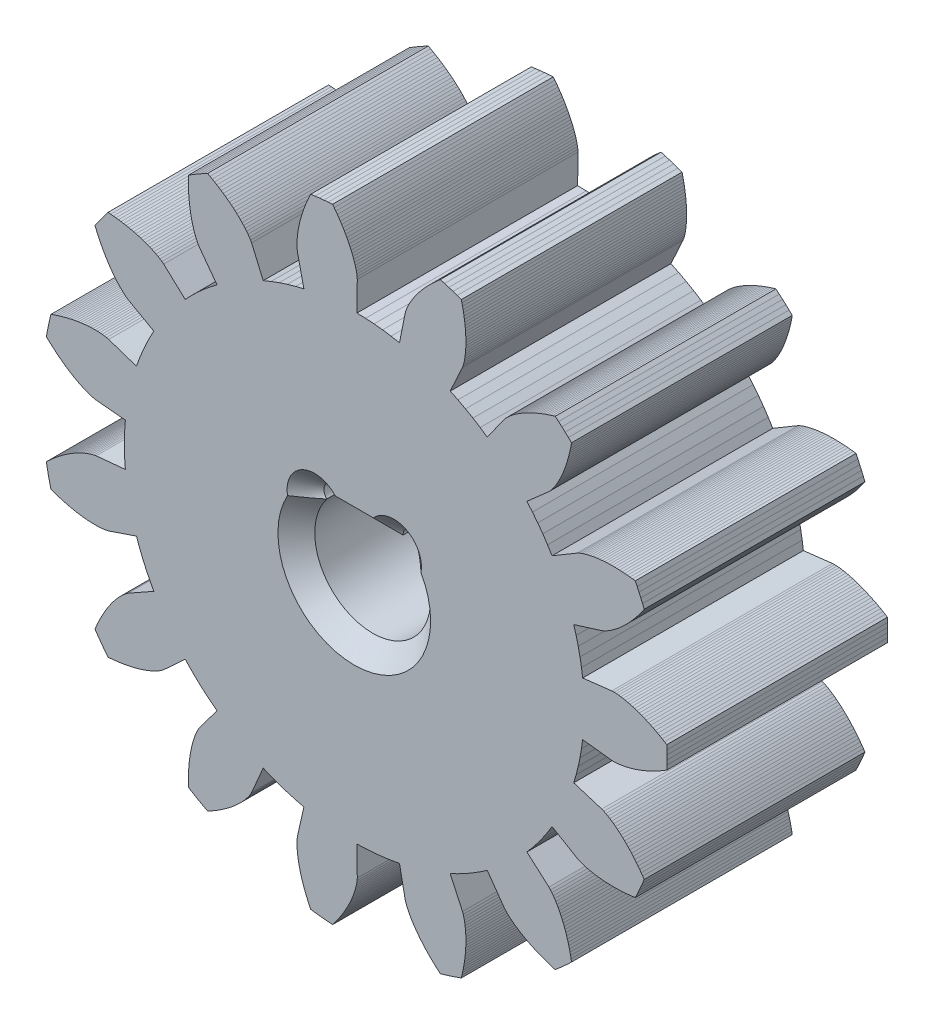
SolidWorks part; units mm, degrees
ref_plane "Front Plane" through (0, 0, 0) normal (0, 0, 1) x (1, 0, 0)
ref_plane "Top Plane" through (0, 0, 0) normal (0, 1, 0) x (1, 0, 0)
ref_plane "Right Plane" through (0, 0, 0) normal (1, 0, 0) x (0, 0, -1)
sketch "Model" plane through (0, 0, 0) normal (0, 0, 1) x (1, 0, 0)
  line L0 (6.2078, -0.7252) -> (7.0001, -0.8177)
  line L1 (7.0001, -0.8177) -> (7.0608, -0.8195)
  line L2 (7.0608, -0.8195) -> (7.122, -0.8168)
  line L3 (7.122, -0.8168) -> (7.1836, -0.8111)
  line L4 (7.1836, -0.8111) -> (7.2454, -0.803)
  line L5 (7.2454, -0.803) -> (7.3074, -0.7927)
  line L6 (7.3074, -0.7927) -> (7.3696, -0.7805)
  line L7 (7.3696, -0.7805) -> (7.4319, -0.7664)
  line L8 (7.4319, -0.7664) -> (7.4943, -0.7506)
  line L9 (7.4943, -0.7506) -> (7.5568, -0.7331)
  line L10 (7.5568, -0.7331) -> (7.6194, -0.714)
  line L11 (7.6194, -0.714) -> (7.6821, -0.6934)
  line L12 (7.6821, -0.6934) -> (7.7448, -0.6713)
  line L13 (7.7448, -0.6713) -> (7.8075, -0.6477)
  line L14 (7.8075, -0.6477) -> (7.8703, -0.6228)
  line L15 (7.8703, -0.6228) -> (7.933, -0.5964)
  line L16 (7.933, -0.5964) -> (7.9957, -0.5686)
  line L17 (7.9957, -0.5686) -> (8.0584, -0.5396)
  line L18 (8.0584, -0.5396) -> (8.121, -0.5091)
  line L19 (8.121, -0.5091) -> (8.1835, -0.4774)
  line L20 (8.1835, -0.4774) -> (8.246, -0.4444)
  line L21 (8.246, -0.4444) -> (8.3083, -0.4102)
  line L22 (8.3083, -0.4102) -> (8.3706, -0.3746)
  line L23 (8.3706, -0.3746) -> (8.4327, -0.3378)
  line L24 (8.4327, -0.3378) -> (8.4947, -0.2998)
  line L25 (8.4947, -0.2998) -> (8.4981, -0.1799)
  line L26 (8.4981, -0.1799) -> (8.4998, -0.06)
  line L27 (8.4998, -0.06) -> (8.4998, 0.06)
  line L28 (8.4998, 0.06) -> (8.4981, 0.1799)
  line L29 (8.4981, 0.1799) -> (8.4947, 0.2998)
  line L30 (8.4947, 0.2998) -> (8.4327, 0.3378)
  line L31 (8.4327, 0.3378) -> (8.3706, 0.3746)
  line L32 (8.3706, 0.3746) -> (8.3083, 0.4102)
  line L33 (8.3083, 0.4102) -> (8.246, 0.4444)
  line L34 (8.246, 0.4444) -> (8.1835, 0.4774)
  line L35 (8.1835, 0.4774) -> (8.121, 0.5091)
  line L36 (8.121, 0.5091) -> (8.0584, 0.5396)
  line L37 (8.0584, 0.5396) -> (7.9957, 0.5686)
  line L38 (7.9957, 0.5686) -> (7.933, 0.5964)
  line L39 (7.933, 0.5964) -> (7.8703, 0.6228)
  line L40 (7.8703, 0.6228) -> (7.8075, 0.6477)
  line L41 (7.8075, 0.6477) -> (7.7448, 0.6713)
  line L42 (7.7448, 0.6713) -> (7.6821, 0.6934)
  line L43 (7.6821, 0.6934) -> (7.6194, 0.714)
  line L44 (7.6194, 0.714) -> (7.5568, 0.7331)
  line L45 (7.5568, 0.7331) -> (7.4943, 0.7506)
  line L46 (7.4943, 0.7506) -> (7.4319, 0.7664)
  line L47 (7.4319, 0.7664) -> (7.3696, 0.7805)
  line L48 (7.3696, 0.7805) -> (7.3074, 0.7927)
  line L49 (7.3074, 0.7927) -> (7.2454, 0.803)
  line L50 (7.2454, 0.803) -> (7.1836, 0.8111)
  line L51 (7.1836, 0.8111) -> (7.122, 0.8168)
  line L52 (7.122, 0.8168) -> (7.0608, 0.8195)
  line L53 (7.0608, 0.8195) -> (7.0001, 0.8177)
  line L54 (7.0001, 0.8177) -> (6.2078, 0.7252)
  line L55 (6.2078, 0.7252) -> (6.1765, 0.9559)
  line L56 (6.1765, 0.9559) -> (6.1366, 1.1853)
  line L57 (6.1366, 1.1853) -> (6.0881, 1.4131)
  line L58 (6.0881, 1.4131) -> (6.0313, 1.6389)
  line L59 (6.0313, 1.6389) -> (5.9661, 1.8624)
  line L60 (5.9661, 1.8624) -> (6.7275, 2.1002)
  line L61 (6.7275, 2.1002) -> (6.7837, 2.1233)
  line L62 (6.7837, 2.1233) -> (6.8385, 2.1506)
  line L63 (6.8385, 2.1506) -> (6.8925, 2.1808)
  line L64 (6.8925, 2.1808) -> (6.9456, 2.2134)
  line L65 (6.9456, 2.2134) -> (6.9981, 2.248)
  line L66 (6.9981, 2.248) -> (7.0499, 2.2845)
  line L67 (7.0499, 2.2845) -> (7.1011, 2.3227)
  line L68 (7.1011, 2.3227) -> (7.1517, 2.3625)
  line L69 (7.1517, 2.3625) -> (7.2017, 2.4039)
  line L70 (7.2017, 2.4039) -> (7.2511, 2.4468)
  line L71 (7.2511, 2.4468) -> (7.3, 2.4911)
  line L72 (7.3, 2.4911) -> (7.3483, 2.5368)
  line L73 (7.3483, 2.5368) -> (7.396, 2.5839)
  line L74 (7.396, 2.5839) -> (7.4432, 2.6322)
  line L75 (7.4432, 2.6322) -> (7.4897, 2.6818)
  line L76 (7.4897, 2.6818) -> (7.5357, 2.7327)
  line L77 (7.5357, 2.7327) -> (7.5811, 2.7847)
  line L78 (7.5811, 2.7847) -> (7.626, 2.838)
  line L79 (7.626, 2.838) -> (7.6702, 2.8924)
  line L80 (7.6702, 2.8924) -> (7.7139, 2.9479)
  line L81 (7.7139, 2.9479) -> (7.7569, 3.0046)
  line L82 (7.7569, 3.0046) -> (7.7993, 3.0624)
  line L83 (7.7993, 3.0624) -> (7.8411, 3.1213)
  line L84 (7.8411, 3.1213) -> (7.8822, 3.1812)
  line L85 (7.8822, 3.1812) -> (7.8366, 3.2921)
  line L86 (7.8366, 3.2921) -> (7.7893, 3.4024)
  line L87 (7.7893, 3.4024) -> (7.7405, 3.512)
  line L88 (7.7405, 3.512) -> (7.6902, 3.6208)
  line L89 (7.6902, 3.6208) -> (7.6384, 3.729)
  line L90 (7.6384, 3.729) -> (7.5663, 3.7385)
  line L91 (7.5663, 3.7385) -> (7.4946, 3.7469)
  line L92 (7.4946, 3.7469) -> (7.4232, 3.754)
  line L93 (7.4232, 3.754) -> (7.3523, 3.76)
  line L94 (7.3523, 3.76) -> (7.2818, 3.7647)
  line L95 (7.2818, 3.7647) -> (7.2118, 3.7682)
  line L96 (7.2118, 3.7682) -> (7.1422, 3.7706)
  line L97 (7.1422, 3.7706) -> (7.0732, 3.7716)
  line L98 (7.0732, 3.7716) -> (7.0046, 3.7715)
  line L99 (7.0046, 3.7715) -> (6.9366, 3.77)
  line L100 (6.9366, 3.77) -> (6.8691, 3.7673)
  line L101 (6.8691, 3.7673) -> (6.8022, 3.7634)
  line L102 (6.8022, 3.7634) -> (6.7359, 3.758)
  line L103 (6.7359, 3.758) -> (6.6703, 3.7514)
  line L104 (6.6703, 3.7514) -> (6.6053, 3.7433)
  line L105 (6.6053, 3.7433) -> (6.5411, 3.7339)
  line L106 (6.5411, 3.7339) -> (6.4776, 3.7229)
  line L107 (6.4776, 3.7229) -> (6.415, 3.7105)
  line L108 (6.415, 3.7105) -> (6.3532, 3.6964)
  line L109 (6.3532, 3.6964) -> (6.2924, 3.6806)
  line L110 (6.2924, 3.6806) -> (6.2326, 3.6628)
  line L111 (6.2326, 3.6628) -> (6.1741, 3.643)
  line L112 (6.1741, 3.643) -> (6.1171, 3.6205)
  line L113 (6.1171, 3.6205) -> (6.0623, 3.5942)
  line L114 (6.0623, 3.5942) -> (5.3761, 3.1874)
  line L115 (5.3761, 3.1874) -> (5.2537, 3.3855)
  line L116 (5.2537, 3.3855) -> (5.1239, 3.5788)
  line L117 (5.1239, 3.5788) -> (4.987, 3.7672)
  line L118 (4.987, 3.7672) -> (4.8433, 3.9504)
  line L119 (4.8433, 3.9504) -> (4.6927, 4.128)
  line L120 (4.6927, 4.128) -> (5.2917, 4.6549)
  line L121 (5.2917, 4.6549) -> (5.3336, 4.6989)
  line L122 (5.3336, 4.6989) -> (5.3726, 4.7462)
  line L123 (5.3726, 4.7462) -> (5.4095, 4.7957)
  line L124 (5.4095, 4.7957) -> (5.4449, 4.8471)
  line L125 (5.4449, 4.8471) -> (5.4787, 4.9)
  line L126 (5.4787, 4.9) -> (5.5112, 4.9544)
  line L127 (5.5112, 4.9544) -> (5.5424, 5.0101)
  line L128 (5.5424, 5.0101) -> (5.5724, 5.0671)
  line L129 (5.5724, 5.0671) -> (5.6013, 5.1253)
  line L130 (5.6013, 5.1253) -> (5.629, 5.1846)
  line L131 (5.629, 5.1846) -> (5.6556, 5.2449)
  line L132 (5.6556, 5.2449) -> (5.6812, 5.3063)
  line L133 (5.6812, 5.3063) -> (5.7056, 5.3687)
  line L134 (5.7056, 5.3687) -> (5.729, 5.4321)
  line L135 (5.729, 5.4321) -> (5.7514, 5.4963)
  line L136 (5.7514, 5.4963) -> (5.7728, 5.5615)
  line L137 (5.7728, 5.5615) -> (5.7931, 5.6275)
  line L138 (5.7931, 5.6275) -> (5.8124, 5.6944)
  line L139 (5.8124, 5.6944) -> (5.8307, 5.7621)
  line L140 (5.8307, 5.7621) -> (5.8479, 5.8306)
  line L141 (5.8479, 5.8306) -> (5.8642, 5.8999)
  line L142 (5.8642, 5.8999) -> (5.8794, 5.9699)
  line L143 (5.8794, 5.9699) -> (5.8937, 6.0407)
  line L144 (5.8937, 6.0407) -> (5.9069, 6.1122)
  line L145 (5.9069, 6.1122) -> (5.82, 6.1949)
  line L146 (5.82, 6.1949) -> (5.732, 6.2764)
  line L147 (5.732, 6.2764) -> (5.6429, 6.3567)
  line L148 (5.6429, 6.3567) -> (5.5526, 6.4357)
  line L149 (5.5526, 6.4357) -> (5.4613, 6.5134)
  line L150 (5.4613, 6.5134) -> (5.3915, 6.4928)
  line L151 (5.3915, 6.4928) -> (5.3226, 6.4712)
  line L152 (5.3226, 6.4712) -> (5.2546, 6.4488)
  line L153 (5.2546, 6.4488) -> (5.1874, 6.4253)
  line L154 (5.1874, 6.4253) -> (5.121, 6.401)
  line L155 (5.121, 6.401) -> (5.0556, 6.3758)
  line L156 (5.0556, 6.3758) -> (4.9911, 6.3496)
  line L157 (4.9911, 6.3496) -> (4.9276, 6.3225)
  line L158 (4.9276, 6.3225) -> (4.865, 6.2944)
  line L159 (4.865, 6.2944) -> (4.8034, 6.2655)
  line L160 (4.8034, 6.2655) -> (4.7429, 6.2355)
  line L161 (4.7429, 6.2355) -> (4.6834, 6.2047)
  line L162 (4.6834, 6.2047) -> (4.625, 6.1729)
  line L163 (4.625, 6.1729) -> (4.5678, 6.1401)
  line L164 (4.5678, 6.1401) -> (4.5117, 6.1063)
  line L165 (4.5117, 6.1063) -> (4.4569, 6.0716)
  line L166 (4.4569, 6.0716) -> (4.4033, 6.0358)
  line L167 (4.4033, 6.0358) -> (4.3512, 5.9989)
  line L168 (4.3512, 5.9989) -> (4.3005, 5.9609)
  line L169 (4.3005, 5.9609) -> (4.2514, 5.9217)
  line L170 (4.2514, 5.9217) -> (4.204, 5.8812)
  line L171 (4.204, 5.8812) -> (4.1586, 5.8392)
  line L172 (4.1586, 5.8392) -> (4.1156, 5.7956)
  line L173 (4.1156, 5.7956) -> (4.0763, 5.7493)
  line L174 (4.0763, 5.7493) -> (3.6149, 5.0985)
  line L175 (3.6149, 5.0985) -> (3.4225, 5.2296)
  line L176 (3.4225, 5.2296) -> (3.2253, 5.3535)
  line L177 (3.2253, 5.3535) -> (3.0236, 5.4699)
  line L178 (3.0236, 5.4699) -> (2.8178, 5.5788)
  line L179 (2.8178, 5.5788) -> (2.608, 5.6799)
  line L180 (2.608, 5.6799) -> (2.9409, 6.4048)
  line L181 (2.9409, 6.4048) -> (2.9613, 6.462)
  line L182 (2.9613, 6.462) -> (2.9776, 6.5211)
  line L183 (2.9776, 6.5211) -> (2.9913, 6.5813)
  line L184 (2.9913, 6.5813) -> (3.0027, 6.6426)
  line L185 (3.0027, 6.6426) -> (3.012, 6.7048)
  line L186 (3.012, 6.7048) -> (3.0196, 6.7677)
  line L187 (3.0196, 6.7677) -> (3.0255, 6.8313)
  line L188 (3.0255, 6.8313) -> (3.0297, 6.8956)
  line L189 (3.0297, 6.8956) -> (3.0324, 6.9604)
  line L190 (3.0324, 6.9604) -> (3.0336, 7.0259)
  line L191 (3.0336, 7.0259) -> (3.0334, 7.0918)
  line L192 (3.0334, 7.0918) -> (3.0317, 7.1583)
  line L193 (3.0317, 7.1583) -> (3.0287, 7.2252)
  line L194 (3.0287, 7.2252) -> (3.0243, 7.2926)
  line L195 (3.0243, 7.2926) -> (3.0186, 7.3604)
  line L196 (3.0186, 7.3604) -> (3.0116, 7.4286)
  line L197 (3.0116, 7.4286) -> (3.0033, 7.4972)
  line L198 (3.0033, 7.4972) -> (2.9937, 7.5662)
  line L199 (2.9937, 7.5662) -> (2.9829, 7.6354)
  line L200 (2.9829, 7.6354) -> (2.9708, 7.7051)
  line L201 (2.9708, 7.7051) -> (2.9575, 7.775)
  line L202 (2.9575, 7.775) -> (2.9429, 7.8452)
  line L203 (2.9429, 7.8452) -> (2.9272, 7.9156)
  line L204 (2.9272, 7.9156) -> (2.9101, 7.9863)
  line L205 (2.9101, 7.9863) -> (2.7972, 8.0266)
  line L206 (2.7972, 8.0266) -> (2.6836, 8.0653)
  line L207 (2.6836, 8.0653) -> (2.5695, 8.1023)
  line L208 (2.5695, 8.1023) -> (2.455, 8.1378)
  line L209 (2.455, 8.1378) -> (2.3399, 8.1716)
  line L210 (2.3399, 8.1716) -> (2.2846, 8.1244)
  line L211 (2.2846, 8.1244) -> (2.2304, 8.0767)
  line L212 (2.2304, 8.0767) -> (2.1773, 8.0284)
  line L213 (2.1773, 8.0284) -> (2.1255, 7.9797)
  line L214 (2.1255, 7.9797) -> (2.0748, 7.9305)
  line L215 (2.0748, 7.9305) -> (2.0253, 7.8808)
  line L216 (2.0253, 7.8808) -> (1.977, 7.8307)
  line L217 (1.977, 7.8307) -> (1.93, 7.7801)
  line L218 (1.93, 7.7801) -> (1.8842, 7.729)
  line L219 (1.8842, 7.729) -> (1.8398, 7.6775)
  line L220 (1.8398, 7.6775) -> (1.7966, 7.6256)
  line L221 (1.7966, 7.6256) -> (1.7548, 7.5732)
  line L222 (1.7548, 7.5732) -> (1.7144, 7.5204)
  line L223 (1.7144, 7.5204) -> (1.6755, 7.4672)
  line L224 (1.6755, 7.4672) -> (1.638, 7.4135)
  line L225 (1.638, 7.4135) -> (1.602, 7.3594)
  line L226 (1.602, 7.3594) -> (1.5677, 7.305)
  line L227 (1.5677, 7.305) -> (1.535, 7.25)
  line L228 (1.535, 7.25) -> (1.5042, 7.1947)
  line L229 (1.5042, 7.1947) -> (1.4752, 7.1389)
  line L230 (1.4752, 7.1389) -> (1.4484, 7.0827)
  line L231 (1.4484, 7.0827) -> (1.424, 7.0259)
  line L232 (1.424, 7.0259) -> (1.4025, 6.9685)
  line L233 (1.4025, 6.9685) -> (1.3854, 6.9102)
  line L234 (1.3854, 6.9102) -> (1.2286, 6.128)
  line L235 (1.2286, 6.128) -> (0.9995, 6.1696)
  line L236 (0.9995, 6.1696) -> (0.769, 6.2025)
  line L237 (0.769, 6.2025) -> (0.5374, 6.2268)
  line L238 (0.5374, 6.2268) -> (0.3051, 6.2425)
  line L239 (0.3051, 6.2425) -> (0.0723, 6.2496)
  line L240 (0.0723, 6.2496) -> (0.0815, 7.0472)
  line L241 (0.0815, 7.0472) -> (0.0769, 7.1078)
  line L242 (0.0769, 7.1078) -> (0.0679, 7.1684)
  line L243 (0.0679, 7.1684) -> (0.0558, 7.229)
  line L244 (0.0558, 7.229) -> (0.0413, 7.2896)
  line L245 (0.0413, 7.2896) -> (0.0246, 7.3502)
  line L246 (0.0246, 7.3502) -> (0.0059, 7.4108)
  line L247 (0.0059, 7.4108) -> (-0.0146, 7.4713)
  line L248 (-0.0146, 7.4713) -> (-0.0369, 7.5317)
  line L249 (-0.0369, 7.5317) -> (-0.0608, 7.5921)
  line L250 (-0.0608, 7.5921) -> (-0.0863, 7.6523)
  line L251 (-0.0863, 7.6523) -> (-0.1134, 7.7125)
  line L252 (-0.1134, 7.7125) -> (-0.1419, 7.7725)
  line L253 (-0.1419, 7.7725) -> (-0.1719, 7.8325)
  line L254 (-0.1719, 7.8325) -> (-0.2033, 7.8922)
  line L255 (-0.2033, 7.8922) -> (-0.2361, 7.9519)
  line L256 (-0.2361, 7.9519) -> (-0.2702, 8.0113)
  line L257 (-0.2702, 8.0113) -> (-0.3057, 8.0706)
  line L258 (-0.3057, 8.0706) -> (-0.3425, 8.1297)
  line L259 (-0.3425, 8.1297) -> (-0.3806, 8.1886)
  line L260 (-0.3806, 8.1886) -> (-0.4199, 8.2473)
  line L261 (-0.4199, 8.2473) -> (-0.4606, 8.3057)
  line L262 (-0.4606, 8.3057) -> (-0.5024, 8.3639)
  line L263 (-0.5024, 8.3639) -> (-0.5455, 8.4218)
  line L264 (-0.5455, 8.4218) -> (-0.5898, 8.4795)
  line L265 (-0.5898, 8.4795) -> (-0.7094, 8.4703)
  line L266 (-0.7094, 8.4703) -> (-0.8288, 8.4595)
  line L267 (-0.8288, 8.4595) -> (-0.9481, 8.447)
  line L268 (-0.9481, 8.447) -> (-1.0672, 8.4327)
  line L269 (-1.0672, 8.4327) -> (-1.1861, 8.4168)
  line L270 (-1.1861, 8.4168) -> (-1.2174, 8.3512)
  line L271 (-1.2174, 8.3512) -> (-1.2475, 8.2856)
  line L272 (-1.2475, 8.2856) -> (-1.2764, 8.22)
  line L273 (-1.2764, 8.22) -> (-1.3039, 8.1544)
  line L274 (-1.3039, 8.1544) -> (-1.3302, 8.0888)
  line L275 (-1.3302, 8.0888) -> (-1.3552, 8.0233)
  line L276 (-1.3552, 8.0233) -> (-1.3789, 7.9578)
  line L277 (-1.3789, 7.9578) -> (-1.4013, 7.8925)
  line L278 (-1.4013, 7.8925) -> (-1.4223, 7.8272)
  line L279 (-1.4223, 7.8272) -> (-1.442, 7.7621)
  line L280 (-1.442, 7.7621) -> (-1.4603, 7.6971)
  line L281 (-1.4603, 7.6971) -> (-1.4772, 7.6322)
  line L282 (-1.4772, 7.6322) -> (-1.4926, 7.5675)
  line L283 (-1.4926, 7.5675) -> (-1.5066, 7.5031)
  line L284 (-1.5066, 7.5031) -> (-1.519, 7.4388)
  line L285 (-1.519, 7.4388) -> (-1.5298, 7.3748)
  line L286 (-1.5298, 7.3748) -> (-1.539, 7.3111)
  line L287 (-1.539, 7.3111) -> (-1.5465, 7.2476)
  line L288 (-1.5465, 7.2476) -> (-1.5522, 7.1845)
  line L289 (-1.5522, 7.1845) -> (-1.556, 7.1217)
  line L290 (-1.556, 7.1217) -> (-1.5576, 7.0595)
  line L291 (-1.5576, 7.0595) -> (-1.5568, 6.9976)
  line L292 (-1.5568, 6.9976) -> (-1.5531, 6.9365)
  line L293 (-1.5531, 6.9365) -> (-1.545, 6.8763)
  line L294 (-1.545, 6.8763) -> (-1.3701, 6.098)
  line L295 (-1.3701, 6.098) -> (-1.5963, 6.0427)
  line L296 (-1.5963, 6.0427) -> (-1.8203, 5.9791)
  line L297 (-1.8203, 5.9791) -> (-2.0417, 5.9071)
  line L298 (-2.0417, 5.9071) -> (-2.2604, 5.8269)
  line L299 (-2.2604, 5.8269) -> (-2.4759, 5.7387)
  line L300 (-2.4759, 5.7387) -> (-2.7919, 6.4711)
  line L301 (-2.7919, 6.4711) -> (-2.8207, 6.5246)
  line L302 (-2.8207, 6.5246) -> (-2.8537, 6.5763)
  line L303 (-2.8537, 6.5763) -> (-2.8893, 6.6267)
  line L304 (-2.8893, 6.6267) -> (-2.9273, 6.6762)
  line L305 (-2.9273, 6.6762) -> (-2.9672, 6.7248)
  line L306 (-2.9672, 6.7248) -> (-3.0089, 6.7725)
  line L307 (-3.0089, 6.7725) -> (-3.0522, 6.8194)
  line L308 (-3.0522, 6.8194) -> (-3.0971, 6.8655)
  line L309 (-3.0971, 6.8655) -> (-3.1435, 6.9109)
  line L310 (-3.1435, 6.9109) -> (-3.1914, 6.9556)
  line L311 (-3.1914, 6.9556) -> (-3.2405, 6.9996)
  line L312 (-3.2405, 6.9996) -> (-3.291, 7.0428)
  line L313 (-3.291, 7.0428) -> (-3.3428, 7.0854)
  line L314 (-3.3428, 7.0854) -> (-3.3958, 7.1272)
  line L315 (-3.3958, 7.1272) -> (-3.45, 7.1684)
  line L316 (-3.45, 7.1684) -> (-3.5054, 7.2088)
  line L317 (-3.5054, 7.2088) -> (-3.5619, 7.2485)
  line L318 (-3.5619, 7.2485) -> (-3.6195, 7.2876)
  line L319 (-3.6195, 7.2876) -> (-3.6783, 7.3259)
  line L320 (-3.6783, 7.3259) -> (-3.7381, 7.3635)
  line L321 (-3.7381, 7.3635) -> (-3.799, 7.4003)
  line L322 (-3.799, 7.4003) -> (-3.8609, 7.4365)
  line L323 (-3.8609, 7.4365) -> (-3.9238, 7.4719)
  line L324 (-3.9238, 7.4719) -> (-3.9877, 7.5065)
  line L325 (-3.9877, 7.5065) -> (-4.0933, 7.4495)
  line L326 (-4.0933, 7.4495) -> (-4.198, 7.391)
  line L327 (-4.198, 7.391) -> (-4.3018, 7.3311)
  line L328 (-4.3018, 7.3311) -> (-4.4048, 7.2696)
  line L329 (-4.4048, 7.2696) -> (-4.507, 7.2067)
  line L330 (-4.507, 7.2067) -> (-4.5089, 7.134)
  line L331 (-4.5089, 7.134) -> (-4.5097, 7.0618)
  line L332 (-4.5097, 7.0618) -> (-4.5094, 6.9902)
  line L333 (-4.5094, 6.9902) -> (-4.5079, 6.919)
  line L334 (-4.5079, 6.919) -> (-4.5052, 6.8484)
  line L335 (-4.5052, 6.8484) -> (-4.5014, 6.7784)
  line L336 (-4.5014, 6.7784) -> (-4.4965, 6.709)
  line L337 (-4.4965, 6.709) -> (-4.4903, 6.6402)
  line L338 (-4.4903, 6.6402) -> (-4.483, 6.572)
  line L339 (-4.483, 6.572) -> (-4.4745, 6.5045)
  line L340 (-4.4745, 6.5045) -> (-4.4647, 6.4377)
  line L341 (-4.4647, 6.4377) -> (-4.4538, 6.3716)
  line L342 (-4.4538, 6.3716) -> (-4.4416, 6.3062)
  line L343 (-4.4416, 6.3062) -> (-4.4281, 6.2416)
  line L344 (-4.4281, 6.2416) -> (-4.4133, 6.1779)
  line L345 (-4.4133, 6.1779) -> (-4.3972, 6.115)
  line L346 (-4.3972, 6.115) -> (-4.3796, 6.053)
  line L347 (-4.3796, 6.053) -> (-4.3607, 5.992)
  line L348 (-4.3607, 5.992) -> (-4.3402, 5.932)
  line L349 (-4.3402, 5.932) -> (-4.3181, 5.8732)
  line L350 (-4.3181, 5.8732) -> (-4.2942, 5.8156)
  line L351 (-4.2942, 5.8156) -> (-4.2684, 5.7595)
  line L352 (-4.2684, 5.7595) -> (-4.2401, 5.7051)
  line L353 (-4.2401, 5.7051) -> (-4.2082, 5.6534)
  line L354 (-4.2082, 5.6534) -> (-3.7319, 5.0135)
  line L355 (-3.7319, 5.0135) -> (-3.9161, 4.871)
  line L356 (-3.9161, 4.871) -> (-4.0948, 4.7218)
  line L357 (-4.0948, 4.7218) -> (-4.2679, 4.5659)
  line L358 (-4.2679, 4.5659) -> (-4.435, 4.4038)
  line L359 (-4.435, 4.4038) -> (-4.596, 4.2355)
  line L360 (-4.596, 4.2355) -> (-5.1825, 4.7761)
  line L361 (-5.1825, 4.7761) -> (-5.2306, 4.8132)
  line L362 (-5.2306, 4.8132) -> (-5.2817, 4.847)
  line L363 (-5.2817, 4.847) -> (-5.3349, 4.8786)
  line L364 (-5.3349, 4.8786) -> (-5.3896, 4.9084)
  line L365 (-5.3896, 4.9084) -> (-5.4458, 4.9365)
  line L366 (-5.4458, 4.9365) -> (-5.5033, 4.9631)
  line L367 (-5.5033, 4.9631) -> (-5.562, 4.9884)
  line L368 (-5.562, 4.9884) -> (-5.6219, 5.0123)
  line L369 (-5.6219, 5.0123) -> (-5.6827, 5.0349)
  line L370 (-5.6827, 5.0349) -> (-5.7446, 5.0562)
  line L371 (-5.7446, 5.0562) -> (-5.8074, 5.0764)
  line L372 (-5.8074, 5.0764) -> (-5.8711, 5.0954)
  line L373 (-5.8711, 5.0954) -> (-5.9357, 5.1132)
  line L374 (-5.9357, 5.1132) -> (-6.0011, 5.1299)
  line L375 (-6.0011, 5.1299) -> (-6.0674, 5.1454)
  line L376 (-6.0674, 5.1454) -> (-6.1344, 5.1598)
  line L377 (-6.1344, 5.1598) -> (-6.2022, 5.1731)
  line L378 (-6.2022, 5.1731) -> (-6.2707, 5.1853)
  line L379 (-6.2707, 5.1853) -> (-6.34, 5.1964)
  line L380 (-6.34, 5.1964) -> (-6.4099, 5.2064)
  line L381 (-6.4099, 5.2064) -> (-6.4805, 5.2153)
  line L382 (-6.4805, 5.2153) -> (-6.5518, 5.2232)
  line L383 (-6.5518, 5.2232) -> (-6.6236, 5.2299)
  line L384 (-6.6236, 5.2299) -> (-6.6962, 5.2356)
  line L385 (-6.6962, 5.2356) -> (-6.7694, 5.1406)
  line L386 (-6.7694, 5.1406) -> (-6.8412, 5.0446)
  line L387 (-6.8412, 5.0446) -> (-6.9117, 4.9475)
  line L388 (-6.9117, 4.9475) -> (-6.9809, 4.8495)
  line L389 (-6.9809, 4.8495) -> (-7.0486, 4.7505)
  line L390 (-7.0486, 4.7505) -> (-7.0208, 4.6833)
  line L391 (-7.0208, 4.6833) -> (-6.9921, 4.617)
  line L392 (-6.9921, 4.617) -> (-6.9627, 4.5517)
  line L393 (-6.9627, 4.5517) -> (-6.9324, 4.4873)
  line L394 (-6.9324, 4.4873) -> (-6.9012, 4.4239)
  line L395 (-6.9012, 4.4239) -> (-6.8693, 4.3615)
  line L396 (-6.8693, 4.3615) -> (-6.8365, 4.3001)
  line L397 (-6.8365, 4.3001) -> (-6.8029, 4.2397)
  line L398 (-6.8029, 4.2397) -> (-6.7685, 4.1804)
  line L399 (-6.7685, 4.1804) -> (-6.7332, 4.1222)
  line L400 (-6.7332, 4.1222) -> (-6.6972, 4.0651)
  line L401 (-6.6972, 4.0651) -> (-6.6603, 4.0092)
  line L402 (-6.6603, 4.0092) -> (-6.6225, 3.9545)
  line L403 (-6.6225, 3.9545) -> (-6.5839, 3.9009)
  line L404 (-6.5839, 3.9009) -> (-6.5445, 3.8487)
  line L405 (-6.5445, 3.8487) -> (-6.5042, 3.7978)
  line L406 (-6.5042, 3.7978) -> (-6.463, 3.7483)
  line L407 (-6.463, 3.7483) -> (-6.4208, 3.7003)
  line L408 (-6.4208, 3.7003) -> (-6.3778, 3.6538)
  line L409 (-6.3778, 3.6538) -> (-6.3336, 3.6091)
  line L410 (-6.3336, 3.6091) -> (-6.2884, 3.5662)
  line L411 (-6.2884, 3.5662) -> (-6.2419, 3.5254)
  line L412 (-6.2419, 3.5254) -> (-6.194, 3.4873)
  line L413 (-6.194, 3.4873) -> (-6.1438, 3.453)
  line L414 (-6.1438, 3.453) -> (-5.4485, 3.0622)
  line L415 (-5.4485, 3.0622) -> (-5.5587, 2.8571)
  line L416 (-5.5587, 2.8571) -> (-5.6613, 2.648)
  line L417 (-5.6613, 2.648) -> (-5.756, 2.4353)
  line L418 (-5.756, 2.4353) -> (-5.8427, 2.2192)
  line L419 (-5.8427, 2.2192) -> (-5.9214, 2)
  line L420 (-5.9214, 2) -> (-6.6771, 2.2553)
  line L421 (-6.6771, 2.2553) -> (-6.7361, 2.2696)
  line L422 (-6.7361, 2.2696) -> (-6.7966, 2.2797)
  line L423 (-6.7966, 2.2797) -> (-6.858, 2.287)
  line L424 (-6.858, 2.287) -> (-6.9201, 2.2919)
  line L425 (-6.9201, 2.2919) -> (-6.9829, 2.2947)
  line L426 (-6.9829, 2.2947) -> (-7.0462, 2.2957)
  line L427 (-7.0462, 2.2957) -> (-7.1101, 2.2948)
  line L428 (-7.1101, 2.2948) -> (-7.1745, 2.2923)
  line L429 (-7.1745, 2.2923) -> (-7.2393, 2.2882)
  line L430 (-7.2393, 2.2882) -> (-7.3045, 2.2826)
  line L431 (-7.3045, 2.2826) -> (-7.3701, 2.2755)
  line L432 (-7.3701, 2.2755) -> (-7.436, 2.2669)
  line L433 (-7.436, 2.2669) -> (-7.5023, 2.2569)
  line L434 (-7.5023, 2.2569) -> (-7.5688, 2.2455)
  line L435 (-7.5688, 2.2455) -> (-7.6357, 2.2327)
  line L436 (-7.6357, 2.2327) -> (-7.7027, 2.2186)
  line L437 (-7.7027, 2.2186) -> (-7.7701, 2.2032)
  line L438 (-7.7701, 2.2032) -> (-7.8377, 2.1865)
  line L439 (-7.8377, 2.1865) -> (-7.9054, 2.1684)
  line L440 (-7.9054, 2.1684) -> (-7.9734, 2.1492)
  line L441 (-7.9734, 2.1492) -> (-8.0415, 2.1286)
  line L442 (-8.0415, 2.1286) -> (-8.1098, 2.1068)
  line L443 (-8.1098, 2.1068) -> (-8.1782, 2.0837)
  line L444 (-8.1782, 2.0837) -> (-8.2468, 2.0594)
  line L445 (-8.2468, 2.0594) -> (-8.275, 1.9428)
  line L446 (-8.275, 1.9428) -> (-8.3016, 1.8259)
  line L447 (-8.3016, 1.8259) -> (-8.3265, 1.7085)
  line L448 (-8.3265, 1.7085) -> (-8.3498, 1.5909)
  line L449 (-8.3498, 1.5909) -> (-8.3714, 1.4729)
  line L450 (-8.3714, 1.4729) -> (-8.3187, 1.4228)
  line L451 (-8.3187, 1.4228) -> (-8.2656, 1.3739)
  line L452 (-8.2656, 1.3739) -> (-8.2121, 1.3262)
  line L453 (-8.2121, 1.3262) -> (-8.1582, 1.2797)
  line L454 (-8.1582, 1.2797) -> (-8.104, 1.2344)
  line L455 (-8.104, 1.2344) -> (-8.0494, 1.1904)
  line L456 (-8.0494, 1.1904) -> (-7.9945, 1.1477)
  line L457 (-7.9945, 1.1477) -> (-7.9392, 1.1062)
  line L458 (-7.9392, 1.1062) -> (-7.8836, 1.066)
  line L459 (-7.8836, 1.066) -> (-7.8278, 1.0272)
  line L460 (-7.8278, 1.0272) -> (-7.7716, 0.9897)
  line L461 (-7.7716, 0.9897) -> (-7.7151, 0.9536)
  line L462 (-7.7151, 0.9536) -> (-7.6584, 0.919)
  line L463 (-7.6584, 0.919) -> (-7.6014, 0.8858)
  line L464 (-7.6014, 0.8858) -> (-7.5441, 0.8541)
  line L465 (-7.5441, 0.8541) -> (-7.4866, 0.824)
  line L466 (-7.4866, 0.824) -> (-7.4288, 0.7955)
  line L467 (-7.4288, 0.7955) -> (-7.3708, 0.7688)
  line L468 (-7.3708, 0.7688) -> (-7.3125, 0.7439)
  line L469 (-7.3125, 0.7439) -> (-7.254, 0.7209)
  line L470 (-7.254, 0.7209) -> (-7.1953, 0.7002)
  line L471 (-7.1953, 0.7002) -> (-7.1362, 0.6818)
  line L472 (-7.1362, 0.6818) -> (-7.0769, 0.6664)
  line L473 (-7.0769, 0.6664) -> (-7.0171, 0.6555)
  line L474 (-7.0171, 0.6555) -> (-6.2229, 0.5813)
  line L475 (-6.2229, 0.5813) -> (-6.2402, 0.3491)
  line L476 (-6.2402, 0.3491) -> (-6.2489, 0.1164)
  line L477 (-6.2489, 0.1164) -> (-6.2489, -0.1164)
  line L478 (-6.2489, -0.1164) -> (-6.2402, -0.3491)
  line L479 (-6.2402, -0.3491) -> (-6.2229, -0.5813)
  line L480 (-6.2229, -0.5813) -> (-7.0171, -0.6555)
  line L481 (-7.0171, -0.6555) -> (-7.0769, -0.6664)
  line L482 (-7.0769, -0.6664) -> (-7.1362, -0.6818)
  line L483 (-7.1362, -0.6818) -> (-7.1953, -0.7002)
  line L484 (-7.1953, -0.7002) -> (-7.254, -0.7209)
  line L485 (-7.254, -0.7209) -> (-7.3125, -0.7439)
  line L486 (-7.3125, -0.7439) -> (-7.3708, -0.7688)
  line L487 (-7.3708, -0.7688) -> (-7.4288, -0.7955)
  line L488 (-7.4288, -0.7955) -> (-7.4866, -0.824)
  line L489 (-7.4866, -0.824) -> (-7.5441, -0.8541)
  line L490 (-7.5441, -0.8541) -> (-7.6014, -0.8858)
  line L491 (-7.6014, -0.8858) -> (-7.6584, -0.919)
  line L492 (-7.6584, -0.919) -> (-7.7151, -0.9536)
  line L493 (-7.7151, -0.9536) -> (-7.7716, -0.9897)
  line L494 (-7.7716, -0.9897) -> (-7.8278, -1.0272)
  line L495 (-7.8278, -1.0272) -> (-7.8836, -1.066)
  line L496 (-7.8836, -1.066) -> (-7.9392, -1.1062)
  line L497 (-7.9392, -1.1062) -> (-7.9945, -1.1477)
  line L498 (-7.9945, -1.1477) -> (-8.0494, -1.1904)
  line L499 (-8.0494, -1.1904) -> (-8.104, -1.2344)
  line L500 (-8.104, -1.2344) -> (-8.1582, -1.2797)
  line L501 (-8.1582, -1.2797) -> (-8.2121, -1.3262)
  line L502 (-8.2121, -1.3262) -> (-8.2656, -1.3739)
  line L503 (-8.2656, -1.3739) -> (-8.3187, -1.4228)
  line L504 (-8.3187, -1.4228) -> (-8.3714, -1.4729)
  line L505 (-8.3714, -1.4729) -> (-8.3498, -1.5909)
  line L506 (-8.3498, -1.5909) -> (-8.3265, -1.7085)
  line L507 (-8.3265, -1.7085) -> (-8.3016, -1.8259)
  line L508 (-8.3016, -1.8259) -> (-8.275, -1.9428)
  line L509 (-8.275, -1.9428) -> (-8.2468, -2.0594)
  line L510 (-8.2468, -2.0594) -> (-8.1782, -2.0837)
  line L511 (-8.1782, -2.0837) -> (-8.1098, -2.1068)
  line L512 (-8.1098, -2.1068) -> (-8.0415, -2.1286)
  line L513 (-8.0415, -2.1286) -> (-7.9734, -2.1492)
  line L514 (-7.9734, -2.1492) -> (-7.9054, -2.1684)
  line L515 (-7.9054, -2.1684) -> (-7.8377, -2.1865)
  line L516 (-7.8377, -2.1865) -> (-7.7701, -2.2032)
  line L517 (-7.7701, -2.2032) -> (-7.7027, -2.2186)
  line L518 (-7.7027, -2.2186) -> (-7.6357, -2.2327)
  line L519 (-7.6357, -2.2327) -> (-7.5688, -2.2455)
  line L520 (-7.5688, -2.2455) -> (-7.5023, -2.2569)
  line L521 (-7.5023, -2.2569) -> (-7.436, -2.2669)
  line L522 (-7.436, -2.2669) -> (-7.3701, -2.2755)
  line L523 (-7.3701, -2.2755) -> (-7.3045, -2.2826)
  line L524 (-7.3045, -2.2826) -> (-7.2393, -2.2882)
  line L525 (-7.2393, -2.2882) -> (-7.1745, -2.2923)
  line L526 (-7.1745, -2.2923) -> (-7.1101, -2.2948)
  line L527 (-7.1101, -2.2948) -> (-7.0462, -2.2957)
  line L528 (-7.0462, -2.2957) -> (-6.9829, -2.2947)
  line L529 (-6.9829, -2.2947) -> (-6.9201, -2.2919)
  line L530 (-6.9201, -2.2919) -> (-6.858, -2.287)
  line L531 (-6.858, -2.287) -> (-6.7966, -2.2797)
  line L532 (-6.7966, -2.2797) -> (-6.7361, -2.2696)
  line L533 (-6.7361, -2.2696) -> (-6.6771, -2.2553)
  line L534 (-6.6771, -2.2553) -> (-5.9214, -2)
  line L535 (-5.9214, -2) -> (-5.8427, -2.2192)
  line L536 (-5.8427, -2.2192) -> (-5.756, -2.4353)
  line L537 (-5.756, -2.4353) -> (-5.6613, -2.648)
  line L538 (-5.6613, -2.648) -> (-5.5587, -2.8571)
  line L539 (-5.5587, -2.8571) -> (-5.4485, -3.0622)
  line L540 (-5.4485, -3.0622) -> (-6.1438, -3.453)
  line L541 (-6.1438, -3.453) -> (-6.194, -3.4873)
  line L542 (-6.194, -3.4873) -> (-6.2419, -3.5254)
  line L543 (-6.2419, -3.5254) -> (-6.2884, -3.5662)
  line L544 (-6.2884, -3.5662) -> (-6.3336, -3.6091)
  line L545 (-6.3336, -3.6091) -> (-6.3778, -3.6538)
  line L546 (-6.3778, -3.6538) -> (-6.4208, -3.7003)
  line L547 (-6.4208, -3.7003) -> (-6.463, -3.7483)
  line L548 (-6.463, -3.7483) -> (-6.5042, -3.7978)
  line L549 (-6.5042, -3.7978) -> (-6.5445, -3.8487)
  line L550 (-6.5445, -3.8487) -> (-6.5839, -3.9009)
  line L551 (-6.5839, -3.9009) -> (-6.6225, -3.9545)
  line L552 (-6.6225, -3.9545) -> (-6.6603, -4.0092)
  line L553 (-6.6603, -4.0092) -> (-6.6972, -4.0651)
  line L554 (-6.6972, -4.0651) -> (-6.7332, -4.1222)
  line L555 (-6.7332, -4.1222) -> (-6.7685, -4.1804)
  line L556 (-6.7685, -4.1804) -> (-6.8029, -4.2397)
  line L557 (-6.8029, -4.2397) -> (-6.8365, -4.3001)
  line L558 (-6.8365, -4.3001) -> (-6.8693, -4.3615)
  line L559 (-6.8693, -4.3615) -> (-6.9012, -4.4239)
  line L560 (-6.9012, -4.4239) -> (-6.9324, -4.4873)
  line L561 (-6.9324, -4.4873) -> (-6.9627, -4.5517)
  line L562 (-6.9627, -4.5517) -> (-6.9921, -4.617)
  line L563 (-6.9921, -4.617) -> (-7.0208, -4.6833)
  line L564 (-7.0208, -4.6833) -> (-7.0486, -4.7505)
  line L565 (-7.0486, -4.7505) -> (-6.9809, -4.8495)
  line L566 (-6.9809, -4.8495) -> (-6.9117, -4.9475)
  line L567 (-6.9117, -4.9475) -> (-6.8412, -5.0446)
  line L568 (-6.8412, -5.0446) -> (-6.7694, -5.1406)
  line L569 (-6.7694, -5.1406) -> (-6.6962, -5.2356)
  line L570 (-6.6962, -5.2356) -> (-6.6236, -5.2299)
  line L571 (-6.6236, -5.2299) -> (-6.5518, -5.2232)
  line L572 (-6.5518, -5.2232) -> (-6.4805, -5.2153)
  line L573 (-6.4805, -5.2153) -> (-6.4099, -5.2064)
  line L574 (-6.4099, -5.2064) -> (-6.34, -5.1964)
  line L575 (-6.34, -5.1964) -> (-6.2707, -5.1853)
  line L576 (-6.2707, -5.1853) -> (-6.2022, -5.1731)
  line L577 (-6.2022, -5.1731) -> (-6.1344, -5.1598)
  line L578 (-6.1344, -5.1598) -> (-6.0674, -5.1454)
  line L579 (-6.0674, -5.1454) -> (-6.0011, -5.1299)
  line L580 (-6.0011, -5.1299) -> (-5.9357, -5.1132)
  line L581 (-5.9357, -5.1132) -> (-5.8711, -5.0954)
  line L582 (-5.8711, -5.0954) -> (-5.8074, -5.0764)
  line L583 (-5.8074, -5.0764) -> (-5.7446, -5.0562)
  line L584 (-5.7446, -5.0562) -> (-5.6827, -5.0349)
  line L585 (-5.6827, -5.0349) -> (-5.6219, -5.0123)
  line L586 (-5.6219, -5.0123) -> (-5.562, -4.9884)
  line L587 (-5.562, -4.9884) -> (-5.5033, -4.9631)
  line L588 (-5.5033, -4.9631) -> (-5.4458, -4.9365)
  line L589 (-5.4458, -4.9365) -> (-5.3896, -4.9084)
  line L590 (-5.3896, -4.9084) -> (-5.3349, -4.8786)
  line L591 (-5.3349, -4.8786) -> (-5.2817, -4.847)
  line L592 (-5.2817, -4.847) -> (-5.2306, -4.8132)
  line L593 (-5.2306, -4.8132) -> (-5.1825, -4.7761)
  line L594 (-5.1825, -4.7761) -> (-4.596, -4.2355)
  line L595 (-4.596, -4.2355) -> (-4.435, -4.4038)
  line L596 (-4.435, -4.4038) -> (-4.2679, -4.5659)
  line L597 (-4.2679, -4.5659) -> (-4.0948, -4.7218)
  line L598 (-4.0948, -4.7218) -> (-3.9161, -4.871)
  line L599 (-3.9161, -4.871) -> (-3.7319, -5.0135)
  line L600 (-3.7319, -5.0135) -> (-4.2082, -5.6534)
  line L601 (-4.2082, -5.6534) -> (-4.2401, -5.7051)
  line L602 (-4.2401, -5.7051) -> (-4.2684, -5.7595)
  line L603 (-4.2684, -5.7595) -> (-4.2942, -5.8156)
  line L604 (-4.2942, -5.8156) -> (-4.3181, -5.8732)
  line L605 (-4.3181, -5.8732) -> (-4.3402, -5.932)
  line L606 (-4.3402, -5.932) -> (-4.3607, -5.992)
  line L607 (-4.3607, -5.992) -> (-4.3796, -6.053)
  line L608 (-4.3796, -6.053) -> (-4.3972, -6.115)
  line L609 (-4.3972, -6.115) -> (-4.4133, -6.1779)
  line L610 (-4.4133, -6.1779) -> (-4.4281, -6.2416)
  line L611 (-4.4281, -6.2416) -> (-4.4416, -6.3062)
  line L612 (-4.4416, -6.3062) -> (-4.4538, -6.3716)
  line L613 (-4.4538, -6.3716) -> (-4.4647, -6.4377)
  line L614 (-4.4647, -6.4377) -> (-4.4745, -6.5045)
  line L615 (-4.4745, -6.5045) -> (-4.483, -6.572)
  line L616 (-4.483, -6.572) -> (-4.4903, -6.6402)
  line L617 (-4.4903, -6.6402) -> (-4.4965, -6.709)
  line L618 (-4.4965, -6.709) -> (-4.5014, -6.7784)
  line L619 (-4.5014, -6.7784) -> (-4.5052, -6.8484)
  line L620 (-4.5052, -6.8484) -> (-4.5079, -6.919)
  line L621 (-4.5079, -6.919) -> (-4.5094, -6.9902)
  line L622 (-4.5094, -6.9902) -> (-4.5097, -7.0618)
  line L623 (-4.5097, -7.0618) -> (-4.5089, -7.134)
  line L624 (-4.5089, -7.134) -> (-4.507, -7.2067)
  line L625 (-4.507, -7.2067) -> (-4.4048, -7.2696)
  line L626 (-4.4048, -7.2696) -> (-4.3018, -7.3311)
  line L627 (-4.3018, -7.3311) -> (-4.198, -7.391)
  line L628 (-4.198, -7.391) -> (-4.0933, -7.4495)
  line L629 (-4.0933, -7.4495) -> (-3.9877, -7.5065)
  line L630 (-3.9877, -7.5065) -> (-3.9238, -7.4719)
  line L631 (-3.9238, -7.4719) -> (-3.8609, -7.4365)
  line L632 (-3.8609, -7.4365) -> (-3.799, -7.4003)
  line L633 (-3.799, -7.4003) -> (-3.7381, -7.3635)
  line L634 (-3.7381, -7.3635) -> (-3.6783, -7.3259)
  line L635 (-3.6783, -7.3259) -> (-3.6195, -7.2876)
  line L636 (-3.6195, -7.2876) -> (-3.5619, -7.2485)
  line L637 (-3.5619, -7.2485) -> (-3.5054, -7.2088)
  line L638 (-3.5054, -7.2088) -> (-3.45, -7.1684)
  line L639 (-3.45, -7.1684) -> (-3.3958, -7.1272)
  line L640 (-3.3958, -7.1272) -> (-3.3428, -7.0854)
  line L641 (-3.3428, -7.0854) -> (-3.291, -7.0428)
  line L642 (-3.291, -7.0428) -> (-3.2405, -6.9996)
  line L643 (-3.2405, -6.9996) -> (-3.1914, -6.9556)
  line L644 (-3.1914, -6.9556) -> (-3.1435, -6.9109)
  line L645 (-3.1435, -6.9109) -> (-3.0971, -6.8655)
  line L646 (-3.0971, -6.8655) -> (-3.0522, -6.8194)
  line L647 (-3.0522, -6.8194) -> (-3.0089, -6.7725)
  line L648 (-3.0089, -6.7725) -> (-2.9672, -6.7248)
  line L649 (-2.9672, -6.7248) -> (-2.9273, -6.6762)
  line L650 (-2.9273, -6.6762) -> (-2.8893, -6.6267)
  line L651 (-2.8893, -6.6267) -> (-2.8537, -6.5763)
  line L652 (-2.8537, -6.5763) -> (-2.8207, -6.5246)
  line L653 (-2.8207, -6.5246) -> (-2.7919, -6.4711)
  line L654 (-2.7919, -6.4711) -> (-2.4759, -5.7387)
  line L655 (-2.4759, -5.7387) -> (-2.2604, -5.8269)
  line L656 (-2.2604, -5.8269) -> (-2.0417, -5.9071)
  line L657 (-2.0417, -5.9071) -> (-1.8203, -5.9791)
  line L658 (-1.8203, -5.9791) -> (-1.5963, -6.0427)
  line L659 (-1.5963, -6.0427) -> (-1.3701, -6.098)
  line L660 (-1.3701, -6.098) -> (-1.545, -6.8763)
  line L661 (-1.545, -6.8763) -> (-1.5531, -6.9365)
  line L662 (-1.5531, -6.9365) -> (-1.5568, -6.9976)
  line L663 (-1.5568, -6.9976) -> (-1.5576, -7.0595)
  line L664 (-1.5576, -7.0595) -> (-1.556, -7.1217)
  line L665 (-1.556, -7.1217) -> (-1.5522, -7.1845)
  line L666 (-1.5522, -7.1845) -> (-1.5465, -7.2476)
  line L667 (-1.5465, -7.2476) -> (-1.539, -7.3111)
  line L668 (-1.539, -7.3111) -> (-1.5298, -7.3748)
  line L669 (-1.5298, -7.3748) -> (-1.519, -7.4388)
  line L670 (-1.519, -7.4388) -> (-1.5066, -7.5031)
  line L671 (-1.5066, -7.5031) -> (-1.4926, -7.5675)
  line L672 (-1.4926, -7.5675) -> (-1.4772, -7.6322)
  line L673 (-1.4772, -7.6322) -> (-1.4603, -7.6971)
  line L674 (-1.4603, -7.6971) -> (-1.442, -7.7621)
  line L675 (-1.442, -7.7621) -> (-1.4223, -7.8272)
  line L676 (-1.4223, -7.8272) -> (-1.4013, -7.8925)
  line L677 (-1.4013, -7.8925) -> (-1.3789, -7.9578)
  line L678 (-1.3789, -7.9578) -> (-1.3552, -8.0233)
  line L679 (-1.3552, -8.0233) -> (-1.3302, -8.0888)
  line L680 (-1.3302, -8.0888) -> (-1.3039, -8.1544)
  line L681 (-1.3039, -8.1544) -> (-1.2764, -8.22)
  line L682 (-1.2764, -8.22) -> (-1.2475, -8.2856)
  line L683 (-1.2475, -8.2856) -> (-1.2174, -8.3512)
  line L684 (-1.2174, -8.3512) -> (-1.1861, -8.4168)
  line L685 (-1.1861, -8.4168) -> (-1.0672, -8.4327)
  line L686 (-1.0672, -8.4327) -> (-0.9481, -8.447)
  line L687 (-0.9481, -8.447) -> (-0.8288, -8.4595)
  line L688 (-0.8288, -8.4595) -> (-0.7094, -8.4703)
  line L689 (-0.7094, -8.4703) -> (-0.5898, -8.4795)
  line L690 (-0.5898, -8.4795) -> (-0.5455, -8.4218)
  line L691 (-0.5455, -8.4218) -> (-0.5024, -8.3639)
  line L692 (-0.5024, -8.3639) -> (-0.4606, -8.3057)
  line L693 (-0.4606, -8.3057) -> (-0.4199, -8.2473)
  line L694 (-0.4199, -8.2473) -> (-0.3806, -8.1886)
  line L695 (-0.3806, -8.1886) -> (-0.3425, -8.1297)
  line L696 (-0.3425, -8.1297) -> (-0.3057, -8.0706)
  line L697 (-0.3057, -8.0706) -> (-0.2702, -8.0113)
  line L698 (-0.2702, -8.0113) -> (-0.2361, -7.9519)
  line L699 (-0.2361, -7.9519) -> (-0.2033, -7.8922)
  line L700 (-0.2033, -7.8922) -> (-0.1719, -7.8325)
  line L701 (-0.1719, -7.8325) -> (-0.1419, -7.7725)
  line L702 (-0.1419, -7.7725) -> (-0.1134, -7.7125)
  line L703 (-0.1134, -7.7125) -> (-0.0863, -7.6523)
  line L704 (-0.0863, -7.6523) -> (-0.0608, -7.5921)
  line L705 (-0.0608, -7.5921) -> (-0.0369, -7.5317)
  line L706 (-0.0369, -7.5317) -> (-0.0146, -7.4713)
  line L707 (-0.0146, -7.4713) -> (0.0059, -7.4108)
  line L708 (0.0059, -7.4108) -> (0.0246, -7.3502)
  line L709 (0.0246, -7.3502) -> (0.0413, -7.2896)
  line L710 (0.0413, -7.2896) -> (0.0558, -7.229)
  line L711 (0.0558, -7.229) -> (0.0679, -7.1684)
  line L712 (0.0679, -7.1684) -> (0.0769, -7.1078)
  line L713 (0.0769, -7.1078) -> (0.0815, -7.0472)
  line L714 (0.0815, -7.0472) -> (0.0723, -6.2496)
  line L715 (0.0723, -6.2496) -> (0.3051, -6.2425)
  line L716 (0.3051, -6.2425) -> (0.5374, -6.2268)
  line L717 (0.5374, -6.2268) -> (0.769, -6.2025)
  line L718 (0.769, -6.2025) -> (0.9995, -6.1696)
  line L719 (0.9995, -6.1696) -> (1.2286, -6.128)
  line L720 (1.2286, -6.128) -> (1.3854, -6.9102)
  line L721 (1.3854, -6.9102) -> (1.4025, -6.9685)
  line L722 (1.4025, -6.9685) -> (1.424, -7.0259)
  line L723 (1.424, -7.0259) -> (1.4484, -7.0827)
  line L724 (1.4484, -7.0827) -> (1.4752, -7.1389)
  line L725 (1.4752, -7.1389) -> (1.5042, -7.1947)
  line L726 (1.5042, -7.1947) -> (1.535, -7.25)
  line L727 (1.535, -7.25) -> (1.5677, -7.305)
  line L728 (1.5677, -7.305) -> (1.602, -7.3594)
  line L729 (1.602, -7.3594) -> (1.638, -7.4135)
  line L730 (1.638, -7.4135) -> (1.6755, -7.4672)
  line L731 (1.6755, -7.4672) -> (1.7144, -7.5204)
  line L732 (1.7144, -7.5204) -> (1.7548, -7.5732)
  line L733 (1.7548, -7.5732) -> (1.7966, -7.6256)
  line L734 (1.7966, -7.6256) -> (1.8398, -7.6775)
  line L735 (1.8398, -7.6775) -> (1.8842, -7.729)
  line L736 (1.8842, -7.729) -> (1.93, -7.7801)
  line L737 (1.93, -7.7801) -> (1.977, -7.8307)
  line L738 (1.977, -7.8307) -> (2.0253, -7.8808)
  line L739 (2.0253, -7.8808) -> (2.0748, -7.9305)
  line L740 (2.0748, -7.9305) -> (2.1255, -7.9797)
  line L741 (2.1255, -7.9797) -> (2.1773, -8.0284)
  line L742 (2.1773, -8.0284) -> (2.2304, -8.0767)
  line L743 (2.2304, -8.0767) -> (2.2846, -8.1244)
  line L744 (2.2846, -8.1244) -> (2.3399, -8.1716)
  line L745 (2.3399, -8.1716) -> (2.455, -8.1378)
  line L746 (2.455, -8.1378) -> (2.5695, -8.1023)
  line L747 (2.5695, -8.1023) -> (2.6836, -8.0653)
  line L748 (2.6836, -8.0653) -> (2.7972, -8.0266)
  line L749 (2.7972, -8.0266) -> (2.9101, -7.9863)
  line L750 (2.9101, -7.9863) -> (2.9272, -7.9156)
  line L751 (2.9272, -7.9156) -> (2.9429, -7.8452)
  line L752 (2.9429, -7.8452) -> (2.9575, -7.775)
  line L753 (2.9575, -7.775) -> (2.9708, -7.7051)
  line L754 (2.9708, -7.7051) -> (2.9829, -7.6354)
  line L755 (2.9829, -7.6354) -> (2.9937, -7.5662)
  line L756 (2.9937, -7.5662) -> (3.0033, -7.4972)
  line L757 (3.0033, -7.4972) -> (3.0116, -7.4286)
  line L758 (3.0116, -7.4286) -> (3.0186, -7.3604)
  line L759 (3.0186, -7.3604) -> (3.0243, -7.2926)
  line L760 (3.0243, -7.2926) -> (3.0287, -7.2252)
  line L761 (3.0287, -7.2252) -> (3.0317, -7.1583)
  line L762 (3.0317, -7.1583) -> (3.0334, -7.0918)
  line L763 (3.0334, -7.0918) -> (3.0336, -7.0259)
  line L764 (3.0336, -7.0259) -> (3.0324, -6.9604)
  line L765 (3.0324, -6.9604) -> (3.0297, -6.8956)
  line L766 (3.0297, -6.8956) -> (3.0255, -6.8313)
  line L767 (3.0255, -6.8313) -> (3.0196, -6.7677)
  line L768 (3.0196, -6.7677) -> (3.012, -6.7048)
  line L769 (3.012, -6.7048) -> (3.0027, -6.6426)
  line L770 (3.0027, -6.6426) -> (2.9913, -6.5813)
  line L771 (2.9913, -6.5813) -> (2.9776, -6.5211)
  line L772 (2.9776, -6.5211) -> (2.9613, -6.462)
  line L773 (2.9613, -6.462) -> (2.9409, -6.4048)
  line L774 (2.9409, -6.4048) -> (2.608, -5.6799)
  line L775 (2.608, -5.6799) -> (2.8178, -5.5788)
  line L776 (2.8178, -5.5788) -> (3.0236, -5.4699)
  line L777 (3.0236, -5.4699) -> (3.2253, -5.3535)
  line L778 (3.2253, -5.3535) -> (3.4225, -5.2296)
  line L779 (3.4225, -5.2296) -> (3.6149, -5.0985)
  line L780 (3.6149, -5.0985) -> (4.0763, -5.7493)
  line L781 (4.0763, -5.7493) -> (4.1156, -5.7956)
  line L782 (4.1156, -5.7956) -> (4.1586, -5.8392)
  line L783 (4.1586, -5.8392) -> (4.204, -5.8812)
  line L784 (4.204, -5.8812) -> (4.2514, -5.9217)
  line L785 (4.2514, -5.9217) -> (4.3005, -5.9609)
  line L786 (4.3005, -5.9609) -> (4.3512, -5.9989)
  line L787 (4.3512, -5.9989) -> (4.4033, -6.0358)
  line L788 (4.4033, -6.0358) -> (4.4569, -6.0716)
  line L789 (4.4569, -6.0716) -> (4.5117, -6.1063)
  line L790 (4.5117, -6.1063) -> (4.5678, -6.1401)
  line L791 (4.5678, -6.1401) -> (4.625, -6.1729)
  line L792 (4.625, -6.1729) -> (4.6834, -6.2047)
  line L793 (4.6834, -6.2047) -> (4.7429, -6.2355)
  line L794 (4.7429, -6.2355) -> (4.8034, -6.2655)
  line L795 (4.8034, -6.2655) -> (4.865, -6.2944)
  line L796 (4.865, -6.2944) -> (4.9276, -6.3225)
  line L797 (4.9276, -6.3225) -> (4.9911, -6.3496)
  line L798 (4.9911, -6.3496) -> (5.0556, -6.3758)
  line L799 (5.0556, -6.3758) -> (5.121, -6.401)
  line L800 (5.121, -6.401) -> (5.1874, -6.4253)
  line L801 (5.1874, -6.4253) -> (5.2546, -6.4488)
  line L802 (5.2546, -6.4488) -> (5.3226, -6.4712)
  line L803 (5.3226, -6.4712) -> (5.3915, -6.4928)
  line L804 (5.3915, -6.4928) -> (5.4613, -6.5134)
  line L805 (5.4613, -6.5134) -> (5.5526, -6.4357)
  line L806 (5.5526, -6.4357) -> (5.6429, -6.3567)
  line L807 (5.6429, -6.3567) -> (5.732, -6.2764)
  line L808 (5.732, -6.2764) -> (5.82, -6.1949)
  line L809 (5.82, -6.1949) -> (5.9069, -6.1122)
  line L810 (5.9069, -6.1122) -> (5.8937, -6.0407)
  line L811 (5.8937, -6.0407) -> (5.8794, -5.9699)
  line L812 (5.8794, -5.9699) -> (5.8642, -5.8999)
  line L813 (5.8642, -5.8999) -> (5.8479, -5.8306)
  line L814 (5.8479, -5.8306) -> (5.8307, -5.7621)
  line L815 (5.8307, -5.7621) -> (5.8124, -5.6944)
  line L816 (5.8124, -5.6944) -> (5.7931, -5.6275)
  line L817 (5.7931, -5.6275) -> (5.7728, -5.5615)
  line L818 (5.7728, -5.5615) -> (5.7514, -5.4963)
  line L819 (5.7514, -5.4963) -> (5.729, -5.4321)
  line L820 (5.729, -5.4321) -> (5.7056, -5.3687)
  line L821 (5.7056, -5.3687) -> (5.6812, -5.3063)
  line L822 (5.6812, -5.3063) -> (5.6556, -5.2449)
  line L823 (5.6556, -5.2449) -> (5.629, -5.1846)
  line L824 (5.629, -5.1846) -> (5.6013, -5.1253)
  line L825 (5.6013, -5.1253) -> (5.5724, -5.0671)
  line L826 (5.5724, -5.0671) -> (5.5424, -5.0101)
  line L827 (5.5424, -5.0101) -> (5.5112, -4.9544)
  line L828 (5.5112, -4.9544) -> (5.4787, -4.9)
  line L829 (5.4787, -4.9) -> (5.4449, -4.8471)
  line L830 (5.4449, -4.8471) -> (5.4095, -4.7957)
  line L831 (5.4095, -4.7957) -> (5.3726, -4.7462)
  line L832 (5.3726, -4.7462) -> (5.3336, -4.6989)
  line L833 (5.3336, -4.6989) -> (5.2917, -4.6549)
  line L834 (5.2917, -4.6549) -> (4.6927, -4.128)
  line L835 (4.6927, -4.128) -> (4.8433, -3.9504)
  line L836 (4.8433, -3.9504) -> (4.987, -3.7672)
  line L837 (4.987, -3.7672) -> (5.1239, -3.5788)
  line L838 (5.1239, -3.5788) -> (5.2537, -3.3855)
  line L839 (5.2537, -3.3855) -> (5.3761, -3.1874)
  line L840 (5.3761, -3.1874) -> (6.0623, -3.5942)
  line L841 (6.0623, -3.5942) -> (6.1171, -3.6205)
  line L842 (6.1171, -3.6205) -> (6.1741, -3.643)
  line L843 (6.1741, -3.643) -> (6.2326, -3.6628)
  line L844 (6.2326, -3.6628) -> (6.2924, -3.6806)
  line L845 (6.2924, -3.6806) -> (6.3532, -3.6964)
  line L846 (6.3532, -3.6964) -> (6.415, -3.7105)
  line L847 (6.415, -3.7105) -> (6.4776, -3.7229)
  line L848 (6.4776, -3.7229) -> (6.5411, -3.7339)
  line L849 (6.5411, -3.7339) -> (6.6053, -3.7433)
  line L850 (6.6053, -3.7433) -> (6.6703, -3.7514)
  line L851 (6.6703, -3.7514) -> (6.7359, -3.758)
  line L852 (6.7359, -3.758) -> (6.8022, -3.7634)
  line L853 (6.8022, -3.7634) -> (6.8691, -3.7673)
  line L854 (6.8691, -3.7673) -> (6.9366, -3.77)
  line L855 (6.9366, -3.77) -> (7.0046, -3.7715)
  line L856 (7.0046, -3.7715) -> (7.0732, -3.7716)
  line L857 (7.0732, -3.7716) -> (7.1422, -3.7706)
  line L858 (7.1422, -3.7706) -> (7.2118, -3.7682)
  line L859 (7.2118, -3.7682) -> (7.2818, -3.7647)
  line L860 (7.2818, -3.7647) -> (7.3523, -3.76)
  line L861 (7.3523, -3.76) -> (7.4232, -3.754)
  line L862 (7.4232, -3.754) -> (7.4946, -3.7469)
  line L863 (7.4946, -3.7469) -> (7.5663, -3.7385)
  line L864 (7.5663, -3.7385) -> (7.6384, -3.729)
  line L865 (7.6384, -3.729) -> (7.6902, -3.6208)
  line L866 (7.6902, -3.6208) -> (7.7405, -3.512)
  line L867 (7.7405, -3.512) -> (7.7893, -3.4024)
  line L868 (7.7893, -3.4024) -> (7.8366, -3.2921)
  line L869 (7.8366, -3.2921) -> (7.8822, -3.1812)
  line L870 (7.8822, -3.1812) -> (7.8411, -3.1213)
  line L871 (7.8411, -3.1213) -> (7.7993, -3.0624)
  line L872 (7.7993, -3.0624) -> (7.7569, -3.0046)
  line L873 (7.7569, -3.0046) -> (7.7139, -2.9479)
  line L874 (7.7139, -2.9479) -> (7.6702, -2.8924)
  line L875 (7.6702, -2.8924) -> (7.626, -2.838)
  line L876 (7.626, -2.838) -> (7.5811, -2.7847)
  line L877 (7.5811, -2.7847) -> (7.5357, -2.7327)
  line L878 (7.5357, -2.7327) -> (7.4897, -2.6818)
  line L879 (7.4897, -2.6818) -> (7.4432, -2.6322)
  line L880 (7.4432, -2.6322) -> (7.396, -2.5839)
  line L881 (7.396, -2.5839) -> (7.3483, -2.5368)
  line L882 (7.3483, -2.5368) -> (7.3, -2.4911)
  line L883 (7.3, -2.4911) -> (7.2511, -2.4468)
  line L884 (7.2511, -2.4468) -> (7.2017, -2.4039)
  line L885 (7.2017, -2.4039) -> (7.1517, -2.3625)
  line L886 (7.1517, -2.3625) -> (7.1011, -2.3227)
  line L887 (7.1011, -2.3227) -> (7.0499, -2.2845)
  line L888 (7.0499, -2.2845) -> (6.9981, -2.248)
  line L889 (6.9981, -2.248) -> (6.9456, -2.2134)
  line L890 (6.9456, -2.2134) -> (6.8925, -2.1808)
  line L891 (6.8925, -2.1808) -> (6.8385, -2.1506)
  line L892 (6.8385, -2.1506) -> (6.7837, -2.1233)
  line L893 (6.7837, -2.1233) -> (6.7275, -2.1002)
  line L894 (6.7275, -2.1002) -> (5.9661, -1.8624)
  line L895 (5.9661, -1.8624) -> (6.0313, -1.6389)
  line L896 (6.0313, -1.6389) -> (6.0881, -1.4131)
  line L897 (6.0881, -1.4131) -> (6.1366, -1.1853)
  line L898 (6.1366, -1.1853) -> (6.1765, -0.9559)
  line L899 (6.1765, -0.9559) -> (6.2078, -0.7252)
  line L900 (-1.118, 1) -> (-1.228, 0.8615)
  line L901 (-1.228, 0.8615) -> (-1.3208, 0.7109)
  line L902 (-1.3208, 0.7109) -> (-1.3953, 0.5505)
  line L903 (-1.3953, 0.5505) -> (-1.4504, 0.3825)
  line L904 (-1.4504, 0.3825) -> (-1.4854, 0.2091)
  line L905 (-1.4854, 0.2091) -> (-1.4996, 0.0328)
  line L906 (-1.4996, 0.0328) -> (-1.4931, -0.1439)
  line L907 (-1.4931, -0.1439) -> (-1.4658, -0.3187)
  line L908 (-1.4658, -0.3187) -> (-1.4181, -0.489)
  line L909 (-1.4181, -0.489) -> (-1.3506, -0.6525)
  line L910 (-1.3506, -0.6525) -> (-1.2645, -0.8069)
  line L911 (-1.2645, -0.8069) -> (-1.1607, -0.9502)
  line L912 (-1.1607, -0.9502) -> (-1.0408, -1.0802)
  line L913 (-1.0408, -1.0802) -> (-0.9064, -1.1951)
  line L914 (-0.9064, -1.1951) -> (-0.7594, -1.2935)
  line L915 (-0.7594, -1.2935) -> (-0.6019, -1.3739)
  line L916 (-0.6019, -1.3739) -> (-0.436, -1.4352)
  line L917 (-0.436, -1.4352) -> (-0.2641, -1.4766)
  line L918 (-0.2641, -1.4766) -> (-0.0884, -1.4974)
  line L919 (-0.0884, -1.4974) -> (0.0884, -1.4974)
  line L920 (0.0884, -1.4974) -> (0.2641, -1.4766)
  line L921 (0.2641, -1.4766) -> (0.436, -1.4352)
  line L922 (0.436, -1.4352) -> (0.6019, -1.3739)
  line L923 (0.6019, -1.3739) -> (0.7594, -1.2935)
  line L924 (0.7594, -1.2935) -> (0.9064, -1.1951)
  line L925 (0.9064, -1.1951) -> (1.0408, -1.0802)
  line L926 (1.0408, -1.0802) -> (1.1607, -0.9502)
  line L927 (1.1607, -0.9502) -> (1.2645, -0.8069)
  line L928 (1.2645, -0.8069) -> (1.3506, -0.6525)
  line L929 (1.3506, -0.6525) -> (1.4181, -0.489)
  line L930 (1.4181, -0.489) -> (1.4658, -0.3187)
  line L931 (1.4658, -0.3187) -> (1.4931, -0.1439)
  line L932 (1.4931, -0.1439) -> (1.4996, 0.0328)
  line L933 (1.4996, 0.0328) -> (1.4854, 0.2091)
  line L934 (1.4854, 0.2091) -> (1.4504, 0.3825)
  line L935 (1.4504, 0.3825) -> (1.3953, 0.5505)
  line L936 (1.3953, 0.5505) -> (1.3208, 0.7109)
  line L937 (1.3208, 0.7109) -> (1.228, 0.8615)
  line L938 (1.228, 0.8615) -> (1.118, 1)
  line L939 (1.118, 1) -> (-1.118, 1)
extrude "Boss-Extrude1" add sketch "Model" along normal blind 6
sketch "Sketch2" plane through (0, 0, 6) normal (0, 0, 1) x (1, 0, 0)
  line L0 (-0.8262, 1.15) -> (0.8262, 1.15)
  arc A0 (-1.2446, 0.9652) -> (1.2446, 0.9652) centre (0, 0) ccw
  arc A1 (-0.8262, 1.15) -> (-1.2446, 0.9652) centre (-1.0762, 1.15) ccw
  arc A2 (1.2446, 0.9652) -> (0.8262, 1.15) centre (1.0762, 1.15) ccw
  point P3 (0, 1.15)
  dimension "D2" = 1.575
  dimension "D3" = 0.25
  dimension "D4" = 0.25
  dimension "D1" = 1.15
extrude "Cut-Extrude1" cut sketch "Sketch2" against normal through all
chamfer "Chamfer1" distance 0.5 angle 45 4 edges at (1.1772, 1.3787, 6) (0, 1.15, 6) (-1.1772, 1.3787, 6) (0, -1.575, 6)
